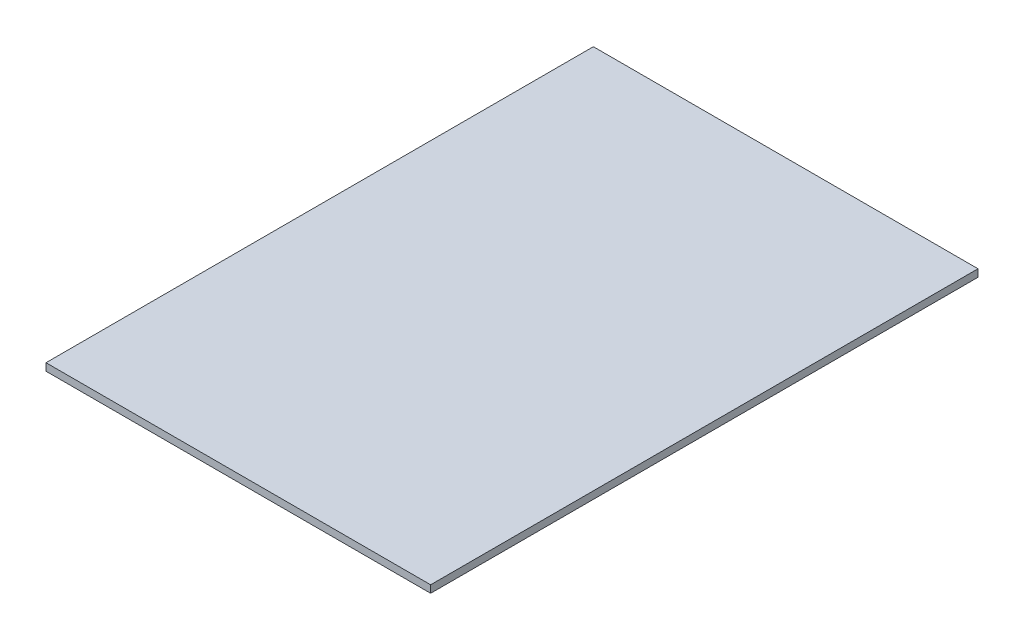
SolidWorks part; units mm, degrees
ref_plane "Front Plane" through (0, 0, 0) normal (0, 0, 1) x (1, 0, 0)
ref_plane "Top Plane" through (0, 0, 0) normal (0, 1, 0) x (1, 0, 0)
ref_plane "Right Plane" through (0, 0, 0) normal (1, 0, 0) x (0, 0, -1)
sketch "Sketch1" plane through (0, 0, 0) normal (0, 1, 0) x (1, 0, 0)
  line L1 (-82.55, 117.475) -> (82.55, 117.475)
  line L2 (-82.55, 117.475) -> (-82.55, -117.475)
  line L3 (-82.55, -117.475) -> (82.55, -117.475)
  line L4 (82.55, 117.475) -> (82.55, -117.475)
  line L5 (-82.55, 117.475) -> (82.55, -117.475) construction
  line L6 (-82.55, -117.475) -> (82.55, 117.475) construction
  point P0 (0, 0)
  dimension "D1" = 234.95
  dimension "D2" = 165.1
extrude "Boss-Extrude1" add sketch "Sketch1" along normal blind 1.5875 and the other way blind 1.5875
